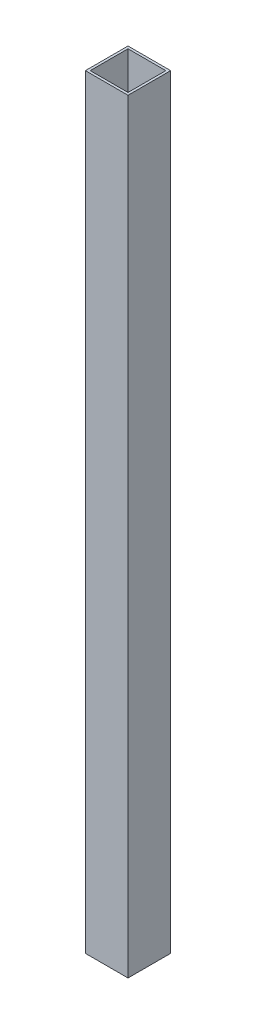
SolidWorks part; units mm, degrees
material "6061 Alloy"
ref_plane "Front Plane" through (0, 0, 0) normal (0, 0, 1) x (1, 0, 0)
ref_plane "Top Plane" through (0, 0, 0) normal (0, 1, 0) x (1, 0, 0)
ref_plane "Right Plane" through (0, 0, 0) normal (1, 0, 0) x (0, 0, -1)
sketch "Sketch1" plane through (0, 0, 0) normal (0, 1, 0) x (1, 0, 0)
  line L9 (12.7, -12.7) -> (-12.7, -12.7)
  line L10 (12.7, -12.7) -> (12.7, 12.7)
  line L11 (12.7, 12.7) -> (-12.7, 12.7)
  line L12 (-12.7, -12.7) -> (-12.7, 12.7)
  line L13 (12.7, -12.7) -> (-12.7, 12.7) construction
  line L14 (12.7, 12.7) -> (-12.7, -12.7) construction
  point P0 (0, 0)
  dimension "D1" = 25.4
extrude "Extrude-Thin1" add sketch "Sketch1" along normal blind 482.6 thin thin type mid plane wall 1.524
